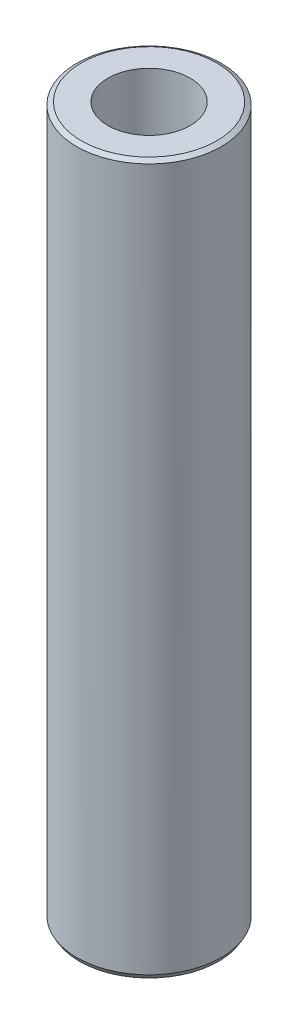
SolidWorks part; units mm, degrees
ref_plane "Front Plane" through (0, 0, 0) normal (0, 0, 1) x (1, 0, 0)
ref_plane "Top Plane" through (0, 0, 0) normal (0, 1, 0) x (1, 0, 0)
ref_plane "Right Plane" through (0, 0, 0) normal (1, 0, 0) x (0, 0, -1)
sketch "Sketch1" plane through (0, 0, 0) normal (0, 1, 0) x (1, 0, 0)
  circle A0 centre (0, 0) radius 50
  dimension "SHAFT_OD" = 100
extrude "Boss-Extrude1" add sketch "Sketch1" along normal blind 490.7777
sketch "Sketch2" plane through (0, 0, 0) normal (0, 1, 0) x (1, 0, 0)
  circle A0 centre (0, 0) radius 28.4619
  dimension "BORE_D" = 56.9237
extrude "Cut-Extrude1" cut sketch "Sketch2" along normal through all
chamfer "Chamfer1" distance 1.8624 angle 60 2 edges at (0, 490.7777, 50) (0, 0, 50) first distance on face at (0, 490.7777, 50) first distance on face at (0, 0, 28.4619)
